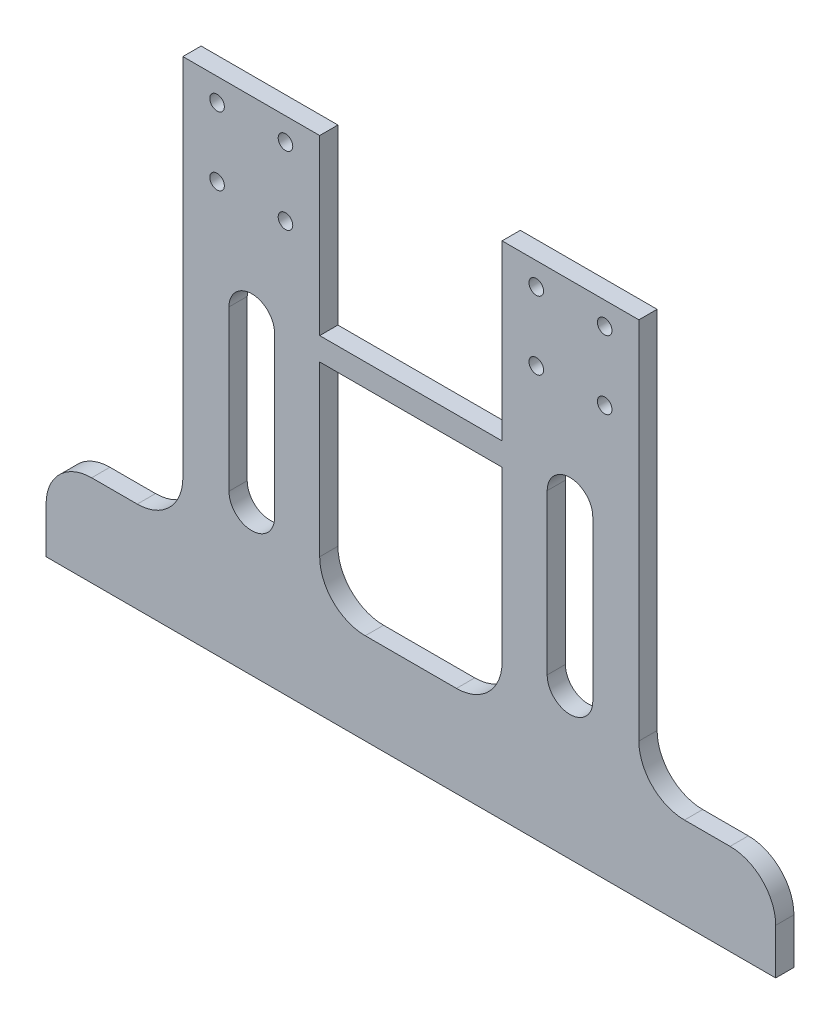
SolidWorks part; units mm, degrees
material "1060 Alloy"
ref_plane "Front Plane" through (0, 0, 0) normal (0, 0, 1) x (1, 0, 0)
ref_plane "Top Plane" through (0, 0, 0) normal (0, 1, 0) x (1, 0, 0)
ref_plane "Right Plane" through (0, 0, 0) normal (1, 0, 0) x (0, 0, -1)
sketch "Sketch1" plane through (0, 0, 0) normal (0, 0, 1) x (1, 0, 0)
  line L0 (20, 20) -> (20, 57)
  line L3 (10, 10) -> (-10, 10)
  line L5 (20, 62) -> (20, 100)
  line L6 (-20, 62) -> (-20, 100)
  line L8 (-50, 20) -> (-50, 100)
  line L9 (-50, 100) -> (-20, 100)
  line L10 (-20, 20) -> (-20, 57)
  line L12 (50, 20) -> (50, 100)
  line L13 (50, 100) -> (20, 100)
  line L15 (-20, 57) -> (20, 57)
  line L17 (-20, 62) -> (20, 62)
  line L19 (-60, 10) -> (-70, 10)
  line L22 (-80, 0) -> (-80, -10)
  line L23 (60, 10) -> (70, 10)
  line L26 (80, 0) -> (80, -10)
  line L27 (-80, -10) -> (-50, -10)
  line L29 (-50, -10) -> (50, -10)
  line L30 (50, -10) -> (80, -10)
  line L31 (0, -10) -> (0, 110.3317) construction
  line L32 (-34.8902, 57.5) -> (-34.8902, 22.5) construction
  line L33 (-29.8902, 57.5) -> (-29.8902, 22.5)
  line L34 (-39.8902, 57.5) -> (-39.8902, 22.5)
  line L35 (34.8902, 57.5) -> (34.8902, 22.5) construction
  line L36 (29.8902, 57.5) -> (29.8902, 22.5)
  line L37 (39.8902, 57.5) -> (39.8902, 22.5)
  circle A0 centre (-42.5, 95) radius 1.6
  circle A1 centre (-27.5, 95) radius 1.6
  circle A2 centre (-42.5, 80) radius 1.6
  circle A3 centre (-27.5, 80) radius 1.6
  circle A4 centre (42.5, 80) radius 1.6
  circle A5 centre (27.5, 80) radius 1.6
  circle A6 centre (27.5, 95) radius 1.6
  circle A7 centre (42.5, 95) radius 1.6
  arc A8 (-29.8902, 57.5) -> (-39.8902, 57.5) centre (-34.8902, 57.5) ccw
  arc A9 (-39.8902, 22.5) -> (-29.8902, 22.5) centre (-34.8902, 22.5) ccw
  arc A10 (29.8902, 57.5) -> (39.8902, 57.5) centre (34.8902, 57.5) cw
  arc A11 (39.8902, 22.5) -> (29.8902, 22.5) centre (34.8902, 22.5) cw
  arc A12 (80, 0) -> (70, 10) centre (70, 0) ccw
  arc A13 (-80, 0) -> (-70, 10) centre (-70, 0) cw
  arc A14 (50, 20) -> (60, 10) centre (60, 20) ccw
  arc A15 (-50, 20) -> (-60, 10) centre (-60, 20) cw
  arc A16 (10, 10) -> (20, 20) centre (10, 20) ccw
  arc A17 (-10, 10) -> (-20, 20) centre (-10, 20) cw
  point P0 (0, 0)
  point P40 (-34.8902, 40)
  point P47 (34.8902, 40)
  point P58 (50, 10)
  dimension "D11" = 7.5
  dimension "D14" = 3.2
  dimension "D15" = 3.2
  dimension "D16" = 7.5
  dimension "D17" = 15
  dimension "D18" = 15
  dimension "D19" = 3.2
  dimension "D20" = 3.2
  dimension "D21" = 10
  dimension "D22" = 10
  dimension "D1" = 30
  dimension "D2" = 110
  dimension "D3" = 30
  dimension "D4" = 110
  dimension "D5" = 100
  dimension "D6" = 20
  dimension "D7" = 38
  dimension "D8" = 5
  dimension "D9" = 30
  dimension "D10" = 30
  dimension "D12" = 5
  dimension "D13" = 5
extrude "Boss-Extrude1" add sketch "Sketch1" along normal blind 4
